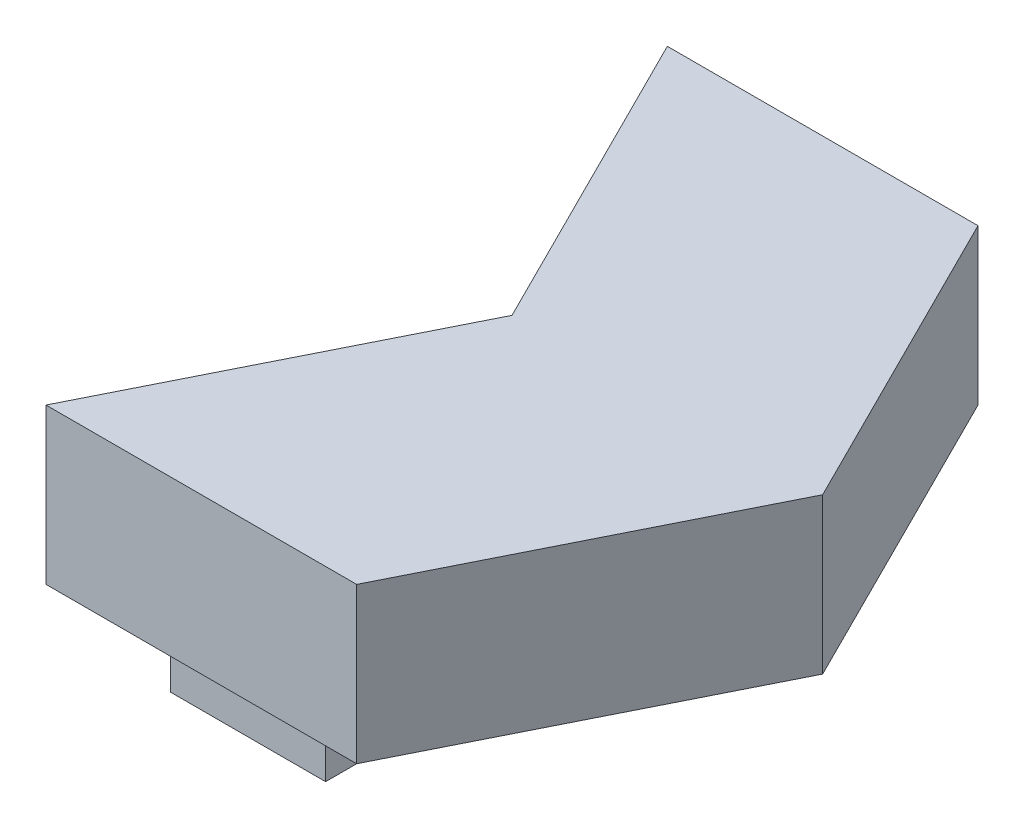
SolidWorks part; units mm, degrees
ref_plane "Front Plane" through (0, 0, 0) normal (0, 0, 1) x (1, 0, 0)
ref_plane "Top Plane" through (0, 0, 0) normal (0, 1, 0) x (1, 0, 0)
ref_plane "Right Plane" through (0, 0, 0) normal (1, 0, 0) x (0, 0, -1)
sketch "Sketch1" plane through (0, 0, 0) normal (0, 1, 0) x (1, 0, 0)
  line L0 (0, 0) -> (12.7, 0)
  line L1 (12.7, 0) -> (19.05, 12.7)
  line L2 (19.05, 12.7) -> (12.7, 25.4)
  line L3 (12.7, 25.4) -> (0, 25.4)
  line L4 (0, 25.4) -> (6.35, 12.7)
  line L5 (6.35, 12.7) -> (0, 0)
  dimension "D1" = 12.7
  dimension "D2" = 25.4
  dimension "D3" = 6.35
  dimension "D5" = 12.7
extrude "Boss-Extrude1" add sketch "Sketch1" along normal blind 6.35
sketch "Sketch2" plane through (0, 0, 0) normal (0, -1, 0) x (1, 0, 0)
  line L0 (19.05, -12.7) -> (6.35, -12.7) construction
  line L1 (6.35, -12.7) -> (0, 0) construction
  circle A0 centre (12.192, -12.7) radius 5.127
  dimension "D1" = 10.254
  dimension "D2" = 5.842
extrude "Cut-Extrude1" cut sketch "Sketch2" against normal blind 2.7 contours A0
sketch "Sketch3" plane through (0, 0, 0) normal (0, -1, 0) x (1, 0, 0)
  line L8 (11.1065, -17.7108) -> (8.8347, -16.5749)
  line L9 (11.1065, -17.7108) -> (9.4026, -21.1185)
  line L10 (8.8347, -16.5749) -> (7.1308, -19.9826)
  line L11 (9.4026, -21.1185) -> (7.1308, -19.9826)
  line L12 (19.05, -12.7) -> (12.7, -25.4) construction
  circle A3 centre (12.192, -12.7) radius 5.127 construction
  dimension "D1" = 2.54
  dimension "D2" = 3.81
extrude "Cut-Extrude2" cut sketch "Sketch3" against normal blind 2.7
ref_plane "MidPlane" through (0, 0, -12.7) normal (0, 0, -1) x (-1, 0, 0)
sketch "Sketch4" plane through (0, 0, 0) normal (0, -1, 0) x (1, 0, 0)
  line L0 (12.7, -25.4) -> (0, -25.4) construction
  line L1 (10.16, -24.13) -> (3.81, -24.13)
  line L2 (10.16, -24.13) -> (10.16, -21.59)
  line L3 (10.16, -21.59) -> (3.81, -21.59)
  line L4 (3.81, -24.13) -> (3.81, -21.59)
  line L5 (0, -55) -> (0, 55) construction
  dimension "D1" = 2.54
  dimension "D2" = 6.35
  dimension "D3" = 1.27
  dimension "D4" = 3.81
extrude "Boss-Extrude2" add sketch "Sketch4" along normal blind 2.54
mirror "Mirror1" about plane through (0, 0, -12.7) normal (0, 0, -1) of "Boss-Extrude2"
ref_point "Point1"
ref_axis "Axis1" through (0, 6.35, -25.4) along (0, 0, 1)
sketch "Sketch5" plane through (0, 6.35, 0) normal (0, 1, 0) x (1, 0, 0)
  line L0 (0, 25.4) -> (0, 0) construction
  line L1 (0, 12.7) -> (19.05, 12.7) construction
equation "\"Arrow Height\"= 1in"
equation "\"Button Height\"= 2in"
equation "\"Button Width\"= 4in"
equation "\"Haptic Diameter\"= 10mm"
equation "\"Haptic Thickness\"= 2.7mm"
equation "\"D2@Sketch1\"=\"Arrow Height\""
equation "\"D5@Sketch1\"=\"Arrow Height\"/2"
equation "\"D1@Sketch2\"=\"Haptic Diameter\"+.01in"
equation "\"D1@Cut-Extrude1\"=\"Haptic Thickness\""
equation "\"D1@Cut-Extrude2\"=\"Haptic Thickness\""
equation "\"Arrow Spacing\"= 1in"
equation "\"Arrow Width\"= 0.75in"
equation "\"Haptic Wire Angle\"= 63.43"
equation "\"Haptic Wire Width\"= .1in"
equation "\"Haptic Wire Height\"= .15in"
